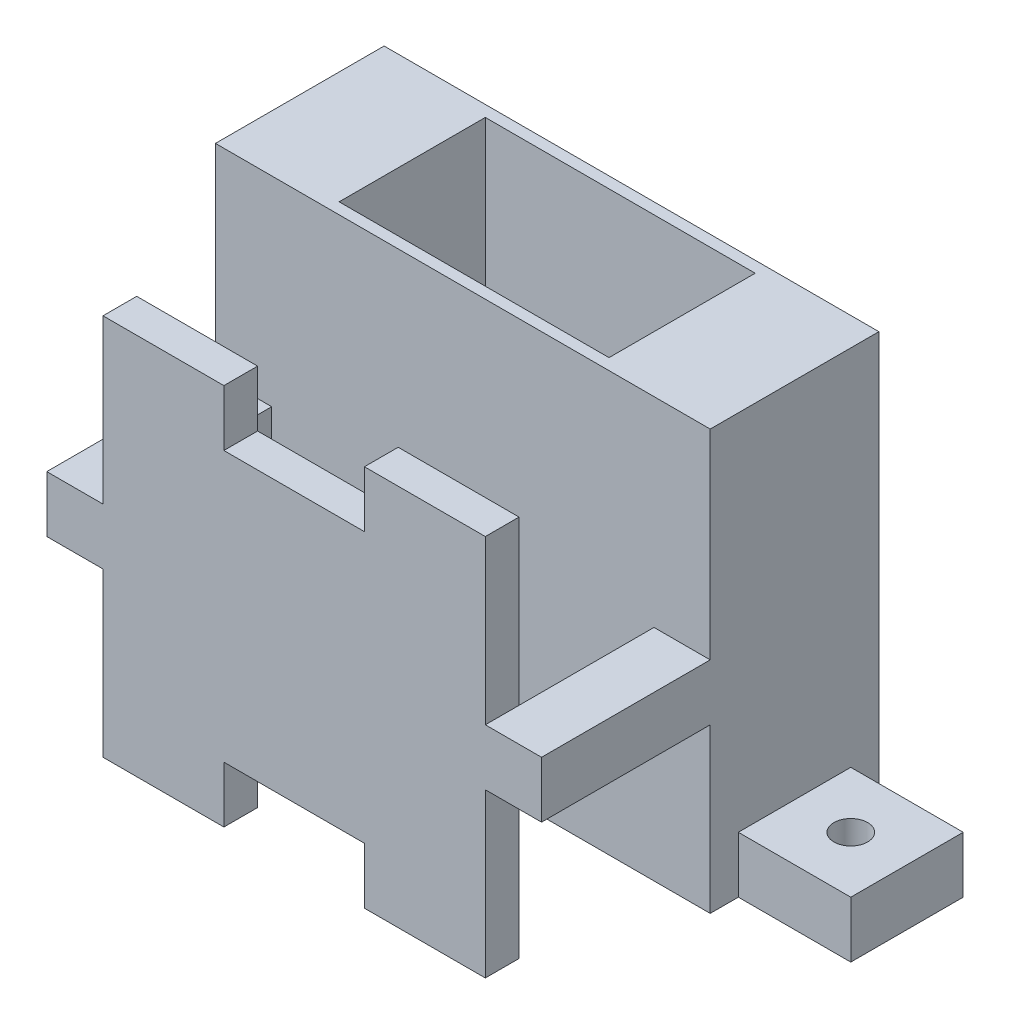
SolidWorks part; units mm, degrees
ref_plane "Front Plane" through (0, 0, 0) normal (0, 0, 1) x (1, 0, 0)
ref_plane "Top Plane" through (0, 0, 0) normal (0, 1, 0) x (1, 0, 0)
ref_plane "Right Plane" through (0, 0, 0) normal (1, 0, 0) x (0, 0, -1)
sketch "Sketch1" plane through (0, 0, 0) normal (0, 0, 1) x (1, 0, 0)
  line L0 (0, 0) -> (0, -34)
  line L1 (0, -34) -> (34, -34)
  line L2 (34, -34) -> (34, 0)
  line L3 (34, 0) -> (0, 0)
  dimension "D1" = 34
  dimension "D2" = 34
extrude "Boss-Extrude1" add sketch "Sketch1" along normal blind 3
sketch "Sketch2" plane through (0, 0, 0) normal (0, 0, -1) x (-1, 0, 0)
  line L0 (-17, 0) -> (-17, -34) construction
  line L1 (-34, 0) -> (0, 0) construction
  line L2 (0, -34) -> (-34, -34) construction
  line L3 (-34, -17) -> (0, -17) construction
  line L4 (-34, -34) -> (-34, 0) construction
  line L5 (0, 0) -> (0, -34) construction
  line L6 (-23.25, -5) -> (-10.75, -5)
  line L7 (-10.75, -5) -> (-10.75, 0)
  line L8 (-10.75, 0) -> (-23.25, 0)
  line L9 (-23.25, -5) -> (-23.25, 0)
  line L10 (-10.75, -29) -> (-10.75, -34)
  line L11 (-23.25, -29) -> (-10.75, -29)
  line L12 (-23.25, -29) -> (-23.25, -34)
  line L13 (-10.75, -34) -> (-23.25, -34)
  point P17 (-17, -5)
  dimension "D1" = 6.25
  dimension "D2" = 5
extrude "Cut-Extrude1" cut sketch "Sketch2" against normal through all contours L8 L9 L6 L7 | L10 L13 L12 L11
sketch "Sketch25" plane through (34, 0, 0) normal (1, 0, 0) x (0, 0, -1)
  line L0 (-3, -17) -> (0, -17) construction
  line L1 (-3, -34) -> (-3, 0) construction
  line L2 (0, -34) -> (0, 0) construction
  line L3 (-3, -17) -> (-3, -14.5)
  line L4 (-3, -14.5) -> (12, -14.5)
  line L11 (12, -14.5) -> (12, -19.5)
  line L12 (-3, -17) -> (-3, -19.5)
  line L13 (-3, -19.5) -> (12, -19.5)
  dimension "D1" = 2.5
  dimension "D2" = 15
  dimension "D4" = 5
extrude "Boss-Extrude2" add sketch "Sketch25" along normal blind 5
sketch "Sketch31" plane through (0, 0, 0) normal (0, 0, -1) x (-1, 0, 0)
  line L0 (-17, -5) -> (-17, -29) construction
  line L1 (-23.25, -5) -> (-10.75, -5) construction
  line L2 (-23.25, -29) -> (-10.75, -29) construction
sketch "Sketch33" plane through (0, 0, 0) normal (-1, 0, 0) x (0, 0, 1)
  line L0 (3, -14.5) -> (-12, -14.5)
  line L1 (-12, -14.5) -> (-12, -19.5)
  line L2 (-12, -19.5) -> (3, -19.5)
  line L3 (3, -19.5) -> (3, -14.5)
  dimension "D1" = 15
extrude "Boss-Extrude4" add sketch "Sketch33" along normal blind 5
sketch "Sketch35" plane through (0, 0, -12) normal (0, 0, -1) x (-1, 0, 0)
  line L6 (-39, -17) -> (-39, 3.2777)
  line L7 (-39, -19.5) -> (-39, -14.5) construction
  line L8 (-39, 3.2777) -> (5, 3.2777)
  line L9 (5, 3.2777) -> (5, -17)
  line L10 (5, -14.5) -> (5, -19.5) construction
  line L11 (5, -17) -> (5, -34.026)
  line L12 (5, -34.026) -> (-39, -34.026)
  line L13 (-39, -34.026) -> (-39, -17)
  dimension "D1" = 44
  dimension "D2" = 44
  dimension "D3" = 37.3037
extrude "Boss-Extrude6" add sketch "Sketch35" along normal blind 15
sketch "Sketch36" plane through (0, 3.2777, 0) normal (0, 1, 0) x (1, 0, 0)
  line L0 (17, 27) -> (17, 12) construction
  line L1 (-5, 27) -> (39, 27) construction
  line L2 (-5, 12) -> (39, 12) construction
  line L3 (5, 26) -> (29, 26)
  line L4 (29, 26) -> (29, 13)
  line L5 (29, 13) -> (5, 13)
  line L6 (5, 26) -> (5, 13)
  point P11 (17, 13)
  point P12 (17, 26)
  dimension "D1" = 12
  dimension "D2" = 13
  dimension "D3" = 1
extrude "Cut-Extrude2" cut sketch "Sketch36" against normal blind 19.5
sketch "Sketch38" plane through (0, -34.026, 0) normal (0, -1, 0) x (-1, 0, 0)
  line L0 (-39, 19.5) -> (5, 19.5) construction
  line L1 (-39, 27) -> (-39, 12) construction
  line L2 (5, 27) -> (5, 12) construction
  line L3 (-39, 24.5) -> (-39, 14.5)
  line L4 (-39, 14.5) -> (-49, 14.5)
  line L5 (-49, 14.5) -> (-49, 17)
  line L6 (-39, 24.5) -> (-49, 24.5)
  line L7 (-49, 24.5) -> (-49, 22)
  line L8 (-17, 12) -> (-17, 27) construction
  line L9 (-39, 12) -> (5, 12) construction
  line L10 (-39, 27) -> (5, 27) construction
  line L11 (5, 24.5) -> (5, 14.5)
  line L12 (5, 24.5) -> (15, 24.5)
  line L13 (15, 24.5) -> (15, 22)
  line L14 (15, 14.5) -> (15, 17)
  line L15 (5, 14.5) -> (15, 14.5)
  line L16 (-49, 22) -> (-49, 17)
  line L17 (15, 22) -> (15, 17)
  line M9 (5, 12) -> (5, 27)
  line M11 (-39, 27) -> (-39, 12)
  dimension "D1" = 10
  dimension "D2" = 2.5
extrude "Boss-Extrude7" add sketch "Sketch38" against normal blind 5 contours L15 L14 L13 L12 M9 | L6 L7 L5 L4 M11 region at (44, -34.026, -19.5) region at (-10, -34.026, -19.5)
sketch "Sketch39" plane through (0, -29.026, 0) normal (0, 1, 0) x (1, 0, 0)
  line L0 (-10, 24.5) -> (-10, 14.5) construction
  line L1 (-5, 24.5) -> (-15, 24.5) construction
  line L2 (-5, 14.5) -> (-15, 14.5) construction
  line L3 (44, 24.5) -> (44, 14.5) construction
  line L4 (39, 24.5) -> (49, 24.5) construction
  line L5 (39, 14.5) -> (49, 14.5) construction
  circle A0 centre (-10, 19.5) radius 1.5
  circle A1 centre (44, 19.5) radius 1.5
extrude "Cut-Extrude3" cut sketch "Sketch39" against normal through all
